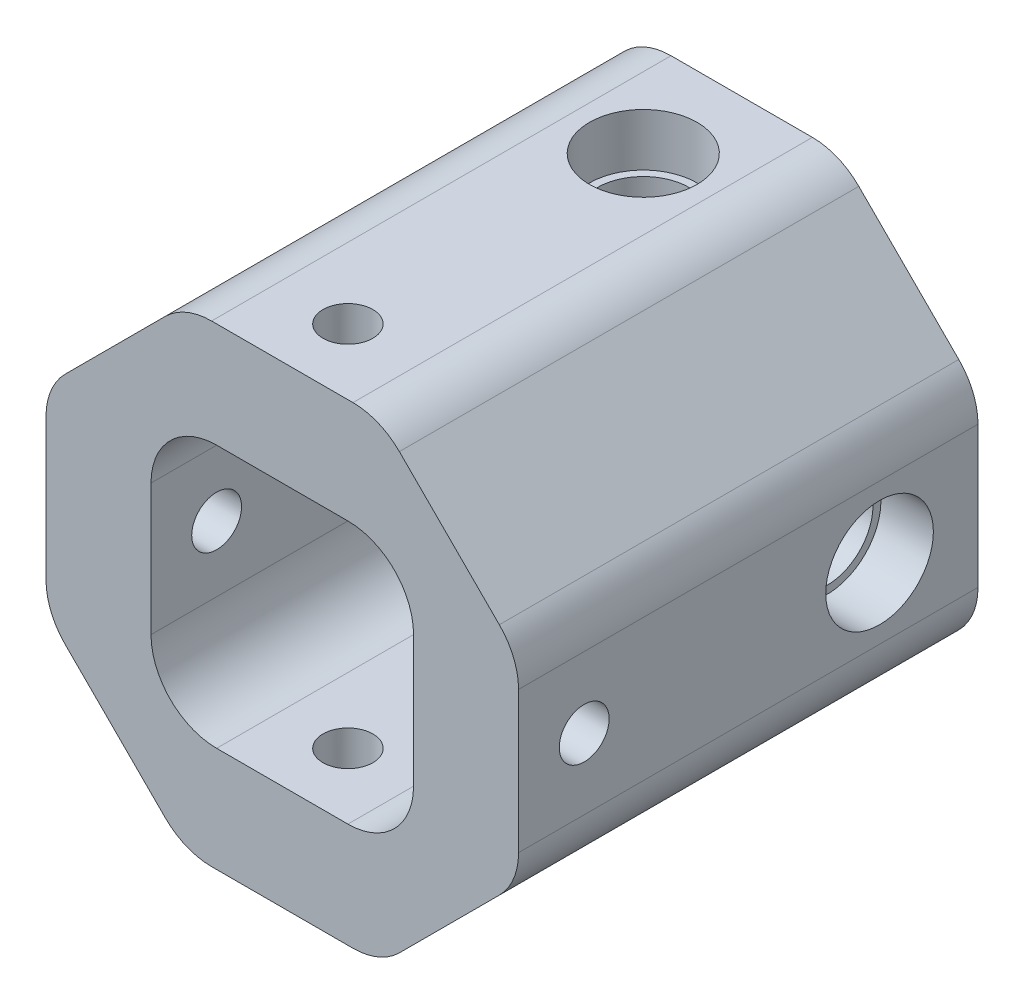
SolidWorks part; units mm, degrees
ref_plane "正面" through (0, 0, 0) normal (0, 0, 1) x (1, 0, 0)
ref_plane "平面" through (0, 0, 0) normal (0, 1, 0) x (1, 0, 0)
ref_plane "右側面" through (0, 0, 0) normal (1, 0, 0) x (0, 0, -1)
sketch "ｽｹｯﾁ1" plane through (0, 0, 0) normal (0, 0, 1) x (1, 0, 0)
  line L0 (7.4558, -18) -> (18, -7.4558)
  line L1 (-18, 7.4558) -> (-18, -7.4558)
  line L2 (-18, -7.4558) -> (-7.4558, -18)
  line L3 (-7.4558, -18) -> (7.4558, -18)
  line L4 (18, -7.4558) -> (18, 7.4558)
  line L5 (18, 7.4558) -> (7.4558, 18)
  line L6 (7.4558, 18) -> (-7.4558, 18)
  line L7 (-7.4558, 18) -> (-18, 7.4558)
  circle A0 centre (0, 0) radius 18 construction
  point P1 (0, -18)
  point P12 (-18, 0)
  dimension "D1" = 18
extrude "ﾎﾞｽ - 押し出し1" add sketch "ｽｹｯﾁ1" along normal mid plane 15
sketch "ｽｹｯﾁ2" plane through (0, 0, 7.5) normal (0, 0, 1) x (1, 0, 0)
  line L0 (7.4558, 18) -> (-7.4558, 18) construction
  line L1 (10, -10) -> (-10, -10)
  line L2 (10, -10) -> (10, 10)
  line L3 (10, 10) -> (-10, 10)
  line L4 (-10, -10) -> (-10, 10)
  line L5 (10, -10) -> (-10, 10) construction
  line L6 (10, 10) -> (-10, -10) construction
  line L7 (18, -7.4558) -> (18, 7.4558) construction
  point P0 (0, 0)
  dimension "D1" = 8
  dimension "D2" = 8
extrude "ｶｯﾄ - 押し出し1" cut sketch "ｽｹｯﾁ2" against normal through all both and the other way through all
fillet "ﾌｨﾚｯﾄ1" radius 5 4 edges at (10, -10, 0) (-10, -10, 0) (10, 10, 0) (-10, 10, 0)
fillet "ﾌｨﾚｯﾄ2" radius 5 8 edges at (18, -7.4558, 0) (7.4558, -18, 0) (-7.4558, -18, 0) (-18, -7.4558, 0) (18, 7.4558, 0) (7.4558, 18, 0) (-18, 7.4558, 0) (-7.4558, 18, 0)
sketch "ｽｹｯﾁ3" plane through (0, -18, 0) normal (0, -1, 0) x (1, 0, 0)
  circle A0 centre (0, 0) radius 4.1
  dimension "D1" = 8.2
extrude "ｶｯﾄ - 押し出し2" cut sketch "ｽｹｯﾁ3" against normal through all both and the other way through all
sketch "ｽｹｯﾁ4" plane through (18, 0, 0) normal (1, 0, 0) x (0, 0, -1)
  circle A0 centre (0, 0) radius 4.1
  dimension "D1" = 8.2
extrude "ｶｯﾄ - 押し出し3" cut sketch "ｽｹｯﾁ4" against normal through all both and the other way through all
sketch "ｽｹｯﾁ5" plane through (0, 0, 7.5) normal (0, 0, 1) x (1, 0, 0)
  line L0 (5, 10) -> (-5, 10) construction
  line L1 (10, -5) -> (10, 5) construction
  line L2 (-5, -10) -> (5, -10) construction
  line L3 (-10, 5) -> (-10, -5) construction
  line L4 (5, 10) -> (-5, 10)
  line L5 (10, -5) -> (10, 5)
  line L6 (-5, -10) -> (5, -10)
  line L7 (-10, 5) -> (-10, -5)
  line L8 (8.9203, -16.5355) -> (16.5355, -8.9203)
  line L9 (18, -5.3848) -> (18, 5.3848)
  line L10 (16.5355, 8.9203) -> (8.9203, 16.5355)
  line L11 (5.3848, 18) -> (-5.3848, 18)
  line L12 (-8.9203, 16.5355) -> (-16.5355, 8.9203)
  line L13 (-18, 5.3848) -> (-18, -5.3848)
  line L14 (-16.5355, -8.9203) -> (-8.9203, -16.5355)
  line L15 (-5.3848, -18) -> (5.3848, -18)
  line L16 (8.9203, -16.5355) -> (16.5355, -8.9203)
  line L17 (18, -5.3848) -> (18, 5.3848)
  line L18 (16.5355, 8.9203) -> (8.9203, 16.5355)
  line L19 (5.3848, 18) -> (-5.3848, 18)
  line L20 (-8.9203, 16.5355) -> (-16.5355, 8.9203)
  line L21 (-18, 5.3848) -> (-18, -5.3848)
  line L22 (-16.5355, -8.9203) -> (-8.9203, -16.5355)
  line L23 (-5.3848, -18) -> (5.3848, -18)
  arc A0 (-5, 10) -> (-10, 5) centre (-5, 5) ccw construction
  arc A1 (-5, 10) -> (-10, 5) centre (-5, 5) ccw
  arc A2 (10, 5) -> (5, 10) centre (5, 5) ccw construction
  arc A3 (5, -10) -> (10, -5) centre (5, -5) ccw construction
  arc A4 (-10, -5) -> (-5, -10) centre (-5, -5) ccw construction
  arc A5 (10, 5) -> (5, 10) centre (5, 5) ccw
  arc A6 (5, -10) -> (10, -5) centre (5, -5) ccw
  arc A7 (-10, -5) -> (-5, -10) centre (-5, -5) ccw
  arc A8 (16.5355, -8.9203) -> (18, -5.3848) centre (13, -5.3848) ccw
  arc A9 (18, 5.3848) -> (16.5355, 8.9203) centre (13, 5.3848) ccw
  arc A10 (8.9203, 16.5355) -> (5.3848, 18) centre (5.3848, 13) ccw
  arc A11 (-5.3848, 18) -> (-8.9203, 16.5355) centre (-5.3848, 13) ccw
  arc A12 (-16.5355, 8.9203) -> (-18, 5.3848) centre (-13, 5.3848) ccw
  arc A13 (-18, -5.3848) -> (-16.5355, -8.9203) centre (-13, -5.3848) ccw
  arc A14 (-8.9203, -16.5355) -> (-5.3848, -18) centre (-5.3848, -13) ccw
  arc A15 (5.3848, -18) -> (8.9203, -16.5355) centre (5.3848, -13) ccw
  arc A16 (16.5355, -8.9203) -> (18, -5.3848) centre (13, -5.3848) ccw
  arc A17 (18, 5.3848) -> (16.5355, 8.9203) centre (13, 5.3848) ccw
  arc A18 (8.9203, 16.5355) -> (5.3848, 18) centre (5.3848, 13) ccw
  arc A19 (-5.3848, 18) -> (-8.9203, 16.5355) centre (-5.3848, 13) ccw
  arc A20 (-16.5355, 8.9203) -> (-18, 5.3848) centre (-13, 5.3848) ccw
  arc A21 (-18, -5.3848) -> (-16.5355, -8.9203) centre (-13, -5.3848) ccw
  arc A22 (-8.9203, -16.5355) -> (-5.3848, -18) centre (-5.3848, -13) ccw
  arc A23 (5.3848, -18) -> (8.9203, -16.5355) centre (5.3848, -13) ccw
  dimension "D1" = 0
extrude "ﾎﾞｽ - 押し出し2" add sketch "ｽｹｯﾁ5" along normal blind 20
sketch "ｽｹｯﾁ6" plane through (0, -18, 0) normal (0, -1, 0) x (1, 0, 0)
  circle A0 centre (0, 0) radius 4.1 construction
  circle A1 centre (0, 0) radius 4.1
  circle A2 centre (0, 0) radius 3.5
  dimension "D1" = 7
extrude "ﾎﾞｽ - 押し出し3" add sketch "ｽｹｯﾁ6" against normal up to surface (8 mm away) from offset 4 up to face at (0, -10, -4.1) offset against normal yes
sketch "ｽｹｯﾁ7" plane through (18, 0, 0) normal (1, 0, 0) x (0, 0, -1)
  circle A0 centre (0, 0) radius 4.1 construction
  circle A1 centre (0, 0) radius 4.1
  circle A2 centre (0, 0) radius 3.5
  dimension "D1" = 7
extrude "ﾎﾞｽ - 押し出し4" add sketch "ｽｹｯﾁ7" along direction (1, 0, 0) on the side against the normal up to surface (8 mm away) from offset 4 up to face at (10, 0, -4.1) offset against normal yes
sketch "ｽｹｯﾁ8" plane through (0, 18, 0) normal (0, 1, 0) x (1, 0, 0)
  circle A0 centre (0, 0) radius 4.1 construction
  circle A1 centre (0, 0) radius 4.1
  circle A2 centre (0, 0) radius 3.5
  dimension "D1" = 7
extrude "ﾎﾞｽ - 押し出し5" add sketch "ｽｹｯﾁ8" against normal up to surface (8 mm away) from offset 4 up to face at (0, 10, 4.1) offset against normal yes
sketch "ｽｹｯﾁ9" plane through (-18, 0, 0) normal (-1, 0, 0) x (0, 0, 1)
  circle A0 centre (0, 0) radius 4.1 construction
  circle A1 centre (0, 0) radius 4.1
  circle A2 centre (0, 0) radius 3.5
  dimension "D1" = 7
extrude "ﾎﾞｽ - 押し出し6" add sketch "ｽｹｯﾁ9" against normal up to surface (8 mm away) from offset 4 up to face at (-10, 0, 4.1) offset against normal yes
sketch "ｽｹｯﾁ10" plane through (-18, 0, 0) normal (-1, 0, 0) x (0, 0, 1)
  line L0 (27.5, 5.3848) -> (27.5, -5.3848) construction
  circle A0 centre (22.5, 0) radius 1.9
  point P4 (0, 0)
  dimension "D1" = 3.8
  dimension "D2" = 5
extrude "ｶｯﾄ - 押し出し4" cut sketch "ｽｹｯﾁ10" against normal through all
sketch "ｽｹｯﾁ11" plane through (0, -18, 0) normal (0, -1, 0) x (1, 0, 0)
  line L0 (-5.3848, 27.5) -> (5.3848, 27.5) construction
  circle A0 centre (0, 22.5) radius 1.9
  point P2 (0, 0)
  dimension "D1" = 3.8
  dimension "D2" = 5
extrude "ｶｯﾄ - 押し出し5" cut sketch "ｽｹｯﾁ11" against normal through all
